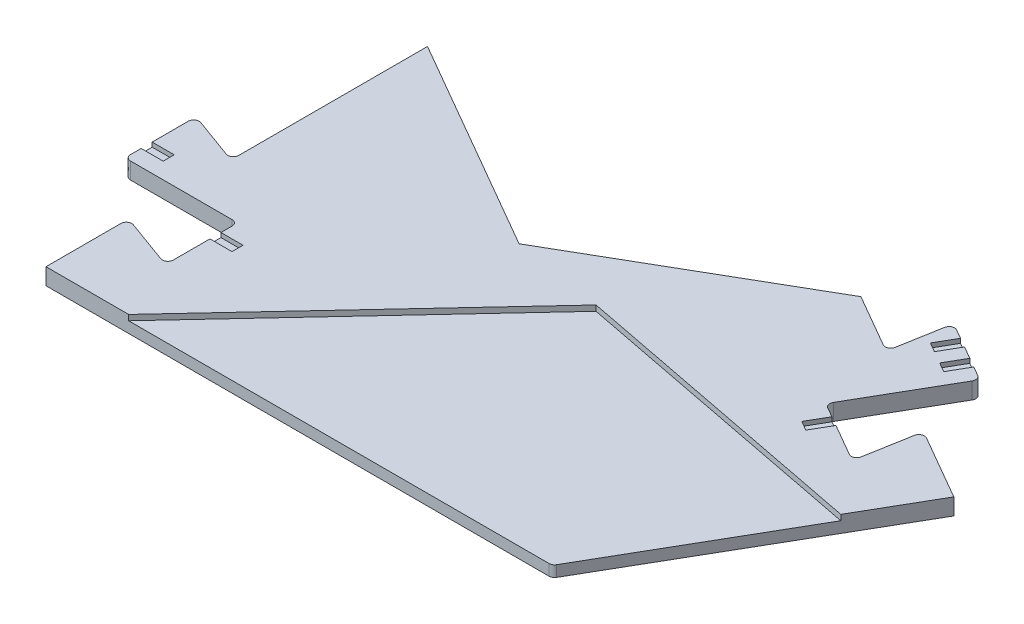
SolidWorks part; units mm, degrees
ref_plane "Přední rovina" through (0, 0, 0) normal (0, 0, 1) x (1, 0, 0)
ref_plane "Horní rovina" through (0, 0, 0) normal (0, 1, 0) x (1, 0, 0)
ref_plane "Pravá rovina" through (0, 0, 0) normal (1, 0, 0) x (0, 0, -1)
sketch "Skica1" plane through (0, 0, 0) normal (0, 1, 0) x (1, 0, 0)
  line L0 (105.5337, 53.6901) -> (118.5241, 46.1901)
  line L1 (118.5241, 46.1901) -> (91.8562, 0)
  line L2 (15, 0) -> (55.9106, 43.8899)
  line L3 (0, 0) -> (0, 15)
  line L4 (0, 15) -> (10.5, 11.1783)
  line L5 (10.5, 11.1783) -> (10.5, 24.2783)
  line L6 (10.5, 24.2783) -> (-9.9505, 24.2783)
  line L7 (55.9106, 43.8899) -> (111.0185, 33.1901)
  line L8 (0, 0) -> (91.8562, 0)
  line L9 (0, 33.5566) -> (-9.9505, 37.1783)
  line L10 (-9.9505, 37.1783) -> (-9.9505, 24.2783)
  line L11 (0, 69.22) -> (0, 33.5566)
  line L12 (0, 69.22) -> (39.3176, 46.52)
  line L13 (39.3176, 46.52) -> (78.6351, 69.22)
  line L14 (105.5337, 53.6901) -> (103.5934, 42.686)
  line L15 (103.5934, 42.686) -> (92.2485, 49.236)
  line L16 (78.6351, 69.22) -> (89.4632, 62.9684)
  line L17 (92.2485, 49.236) -> (102.4737, 66.9466)
  line L18 (89.4632, 62.9684) -> (91.302, 73.3966)
  line L19 (91.302, 73.3966) -> (102.4737, 66.9466)
  line L20 (0, 69.22) -> (0, 0) construction
  line L21 (78.6351, 69.22) -> (118.5241, 46.1901) construction
  point P0 (94.9308, 5.3253)
  dimension "D1" = 90
  dimension "D2" = 15
  dimension "D3" = 91.8562
  dimension "D4" = 70
  dimension "D5" = 15
  dimension "D6" = 122
  dimension "D7" = 69.22
  dimension "D8" = 60
  dimension "D9" = 13
  dimension "D10" = 120
  dimension "D11" = 45.4
  dimension "D12" = 45.4
  dimension "D13" = 69.22
  dimension "D14" = 70
  dimension "D15" = 70
  dimension "D16" = 120
  dimension "D17" = 120
  dimension "D18" = 13.1
  dimension "D19" = 12.9
  dimension "D20" = 10.5
  dimension "D21" = 12.9
  dimension "D22" = 13.1
  dimension "D23" = 10.5
  dimension "D24" = 15
extrude "Přidat vysunutím1" add sketch "Skica1" along normal blind 3 contours L19 L18 L16 L13 L12 L11 L9 L10 L6 L5 L4 L3 L8 L2 L7 L1 L0 L14 L15 L17 region at (43.6515, 0, -40.5739)
extrude "Přidat vysunutím2" add sketch "Skica1<3>" along normal blind 2 contours L2 L8 L1 L7 region at (66.2955, 0, -18.7917)
sketch "Skica1<3>" plane through (0, 0, 0) normal (0, 1, 0) x (1, 0, 0) same geometry as "Skica1"
fillet "Zaoblit1" radius 1 12 edges at (0, 1.5, -33.5566) (-9.9505, 1.5, -37.1783) (10.5, 1.5, -24.2783) (-9.9505, 1.5, -24.2783) (10.5, 1.5, -11.1783) (0, 1.5, -15) (105.5337, 1.5, -53.6901) (103.5934, 1.5, -42.686) (92.2485, 1.5, -49.236) (89.4632, 1.5, -62.9684) (91.302, 1.5, -73.3966) (102.4737, 1.5, -66.9466)
fillet "Zaoblit2" radius 1 1 edges at (91.8562, 1, 0)
sketch "Skica2" plane through (0, 3, 0) normal (0, 1, 0) x (1, 0, 0)
  line L0 (-9.9505, 30.5142) -> (43.4429, 30.5142) construction
  line L1 (-9.9505, 35.7502) -> (-9.9505, 25.2783) construction
  line L2 (15, 0) -> (55.9106, 43.8899) construction
  line L3 (-9.9505, 29.2142) -> (-5.9505, 29.2142)
  line L4 (-5.9505, 29.2142) -> (-5.9505, 27.2142)
  line L5 (-5.9505, 27.2142) -> (-9.9505, 27.2142)
  line L6 (-9.9505, 27.2142) -> (-9.9505, 29.2142)
  line L7 (10.5, 17.9424) -> (31.7245, 17.9424) construction
  line L8 (10.5, 12.6065) -> (10.5, 23.2783) construction
  line L9 (10.5, 19.2424) -> (14.5, 19.2424)
  line L10 (14.5, 19.2424) -> (14.5, 21.2424)
  line L11 (14.5, 21.2424) -> (10.5, 21.2424)
  line L12 (10.5, 21.2424) -> (10.5, 19.2424)
  line L13 (97.0732, 70.0646) -> (84.1483, 47.678) construction
  line L14 (92.5388, 72.6825) -> (101.6077, 67.4466) construction
  line L15 (92.7485, 50.102) -> (101.9737, 66.0806) construction
  line L16 (97.7355, 46.068) -> (93.2551, 38.3076) construction
  line L17 (102.3566, 43.4) -> (93.1145, 48.736) construction
  line L18 (94.2154, 71.7146) -> (92.2154, 68.2505)
  line L19 (92.2154, 68.2505) -> (93.9474, 67.2505)
  line L20 (93.9474, 67.2505) -> (95.9474, 70.7146)
  line L21 (95.9474, 70.7146) -> (94.2154, 71.7146)
  line L22 (96.1991, 65.9505) -> (98.1991, 69.4146)
  line L23 (97.9311, 64.9505) -> (96.1991, 65.9505)
  line L24 (99.9311, 68.4146) -> (97.9311, 64.9505)
  line L25 (98.1991, 69.4146) -> (99.9311, 68.4146)
  line L26 (96.6097, 46.718) -> (94.6097, 43.2539)
  line L27 (94.6097, 43.2539) -> (92.8777, 44.2539)
  line L28 (92.8777, 44.2539) -> (94.8777, 47.718)
  line L29 (94.8777, 47.718) -> (96.6097, 46.718)
  dimension "D1" = 1.3
  dimension "D2" = 2
  dimension "D3" = 4
  dimension "D4" = 4
  dimension "D5" = 2
  dimension "D6" = 1.3
  dimension "D7" = 2
  dimension "D8" = 4
  dimension "D9" = 1.3
  dimension "D10" = 2
  dimension "D11" = 4
  dimension "D12" = 1.3
extrude "Odebrat vysunutím1" cut sketch "Skica2" against normal blind 0.8
